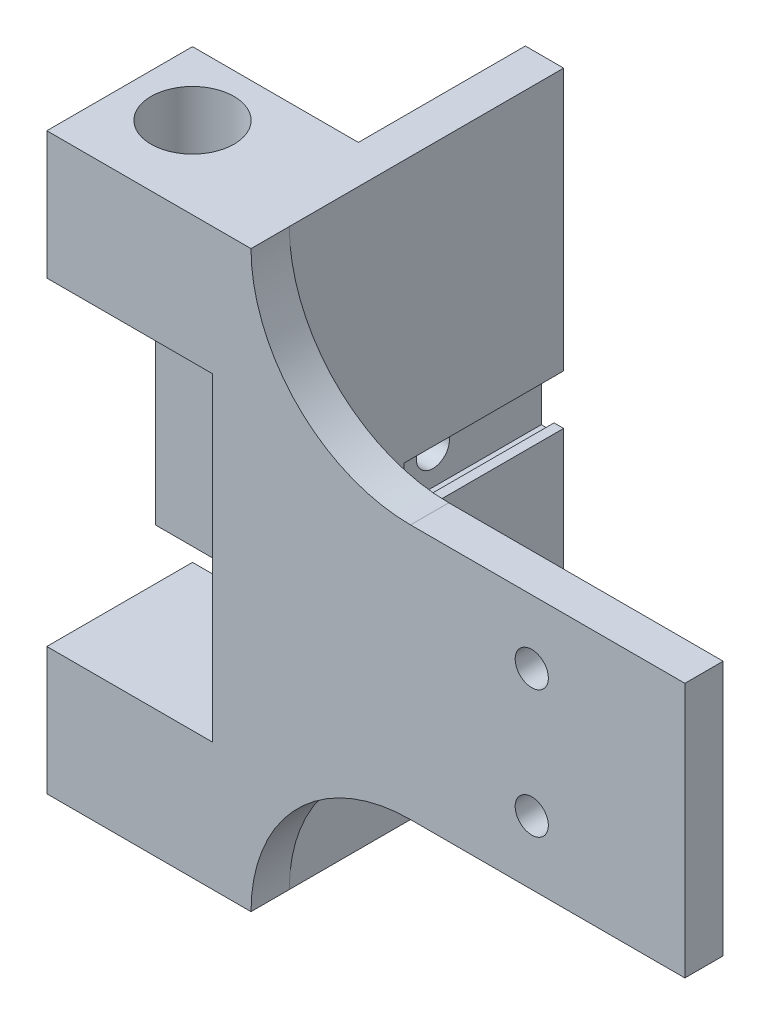
SolidWorks part; units mm, degrees
ref_plane "Front Plane" through (0, 0, 0) normal (0, 0, 1) x (1, 0, 0)
ref_plane "Top Plane" through (0, 0, 0) normal (0, 1, 0) x (1, 0, 0)
ref_plane "Right Plane" through (0, 0, 0) normal (1, 0, 0) x (0, 0, -1)
sketch "Sketch1" plane through (0, 0, 0) normal (0, 0, 1) x (1, 0, 0)
  line L1 (0, 0) -> (74, 0)
  line L2 (0, 0) -> (0, 90)
  line L3 (0, 90) -> (74, 90)
  line L4 (74, 0) -> (74, 90)
  circle A0 centre (50, 55) radius 2.6
  circle A1 centre (50, 35) radius 2.6
  point P9 (0, 0)
  point P10 (0, 0)
  dimension "D3" = 5.2
  dimension "D4" = 5.2
  dimension "D1" = 90
  dimension "D2" = 74
  dimension "D5" = 50
  dimension "D6" = 50
  dimension "D7" = 20
  dimension "D8" = 35
extrude "Boss-Extrude1" add sketch "Sketch1" along normal blind 6
sketch "Sketch2" plane through (0, 0, 0) normal (0, 0, -1) x (-1, 0, 0)
  line L0 (0, 0) -> (-74, 0) construction
  line L1 (0, 90) -> (-6, 90)
  line L2 (0, 90) -> (0, 0)
  line L3 (0, 0) -> (-6, 0)
  line L4 (-6, 90) -> (-6, 0)
  dimension "D1" = 6
extrude "Boss-Extrude2" add sketch "Sketch2" along normal blind 43
sketch "Sketch4" plane through (0, 0, 0) normal (0, 0, -1) x (-1, 0, 0)
  line L0 (-6, 90) -> (-6, 0) construction
  line L1 (-74, 90) -> (-6, 90)
  line L2 (-74, 90) -> (-74, 65)
  line L3 (-74, 65) -> (-6, 65)
  line L4 (-6, 90) -> (-6, 65)
  line L5 (-6, 90) -> (-6, 0) construction
  line L6 (-74, 0) -> (-6, 0)
  line L7 (-74, 0) -> (-74, 25)
  line L8 (-74, 25) -> (-6, 25)
  line L9 (-6, 0) -> (-6, 25)
  dimension "D1" = 25
  dimension "D2" = 25
extrude "Cut-Extrude3" cut sketch "Sketch4" against normal blind 6
fillet "Fillet2" radius 25 2 edges at (6, 65, 3) (6, 25, 3)
sketch "Sketch5" plane through (0, 0, 0) normal (-1, 0, 0) x (0, 0, 1)
  line L0 (-43, 0) -> (-43, 90) construction
  line L1 (-43, 60) -> (-9, 60)
  line L2 (-43, 60) -> (-43, 30)
  line L3 (-43, 30) -> (-9, 30)
  line L4 (-9, 60) -> (-9, 30)
  line L5 (6, 0) -> (-43, 0) construction
  line L6 (6, 90) -> (6, 0) construction
  dimension "D1" = 30
  dimension "D2" = 30
  dimension "D3" = 15
extrude "Boss-Extrude3" add sketch "Sketch5" along normal blind 24
sketch "Sketch3" plane through (0, 0, 0) normal (-1, 0, 0) x (0, 0, 1)
  line L0 (6, 90) -> (6, 0) construction
  line L1 (6, 0) -> (-43, 0) construction
  circle A0 centre (-26, 45) radius 2.6
  dimension "D2" = 5.2
  dimension "D1" = 32
  dimension "D3" = 45
extrude "Cut-Extrude1" cut sketch "Sketch3" against normal through all both and the other way through all
sketch "Sketch6" plane through (0, 60, 0) normal (0, 1, 0) x (1, 0, 0)
  line L0 (-24, 9) -> (-24, 43) construction
  line L1 (-3.75, 40) -> (-21, 40)
  line L2 (-3.75, 40) -> (-3.75, 12)
  line L3 (-3.75, 12) -> (-21, 12)
  line L4 (-21, 40) -> (-21, 12)
  line L5 (-24, 9) -> (0, 9) construction
  line L7 (-24, 43) -> (0, 43) construction
  line L8 (0, 9) -> (0, 43) construction
  dimension "D1" = 3
  dimension "D2" = 3
  dimension "D3" = 3
  dimension "D4" = 3.75
extrude "Cut-Extrude4" cut sketch "Sketch6" against normal through all
sketch "Sketch7" plane through (0, 0, -43) normal (0, 0, -1) x (-1, 0, 0)
  line L1 (-2.5, 50.15) -> (-4.5, 50.15)
  line L2 (-2.5, 50.15) -> (-2.5, 39.85)
  line L3 (-2.5, 39.85) -> (-4.5, 39.85)
  line L4 (-4.5, 50.15) -> (-4.5, 48.9)
  line L5 (24, 60) -> (0, 60) construction
  line L6 (-6, 90) -> (-6, 0) construction
  line L7 (-4.5, 41.1) -> (-4.5, 39.85)
  line L8 (-4.5, 48.9) -> (-7.5, 48.9)
  line L10 (-4.5, 41.1) -> (-7.5, 41.1)
  line L11 (-7.5, 48.9) -> (-7.5, 41.1)
  dimension "D1" = 10.3
  dimension "D2" = 2
  dimension "D3" = 9.85
  dimension "D4" = 1.5
  dimension "D6" = 1.25
  dimension "D5" = 1.25
extrude "Cut-Extrude5" cut sketch "Sketch7" against normal blind 25
sketch "Sketch8" plane through (0, 0, 0) normal (-1, 0, 0) x (0, 0, 1)
  line L0 (6, 90) -> (6, 0) construction
  line L1 (6, 0) -> (-16.83, 0)
  line L2 (6, 0) -> (6, 20)
  line L3 (6, 20) -> (-16.83, 20)
  line L4 (-16.83, 0) -> (-16.83, 20)
  line L5 (6, 90) -> (-43, 90) construction
  line L6 (-16.83, 70) -> (6, 70)
  line L7 (-16.83, 70) -> (-16.83, 90)
  line L8 (-16.83, 90) -> (6, 90)
  line L9 (6, 70) -> (6, 90)
  dimension "D1" = 20
  dimension "D2" = 0
  dimension "D3" = 22.83
  dimension "D4" = 0
  dimension "D5" = 0
  dimension "D6" = 20
  dimension "D7" = 22.83
extrude "Boss-Extrude4" add sketch "Sketch8" along normal blind 26
sketch "Sketch9" plane through (0, 0, 0) normal (0, -1, 0) x (1, 0, 0)
  line L0 (-26, -16.83) -> (0, -16.83) construction
  line L1 (-26, -16.83) -> (-26, 6) construction
  circle A0 centre (-16, -6.83) radius 6.5
  dimension "D1" = 13
  dimension "D2" = 10
  dimension "D3" = 10
extrude "Cut-Extrude6" cut sketch "Sketch9" against normal blind 10
sketch "Sketch10" plane through (0, 90, 0) normal (0, 1, 0) x (1, 0, 0)
  line L0 (-26, -6) -> (-26, 16.83) construction
  line L1 (-26, 16.83) -> (0, 16.83) construction
  circle A0 centre (-16, 6.83) radius 6.5
  dimension "D1" = 13
  dimension "D2" = 10
  dimension "D3" = 10
extrude "Cut-Extrude7" cut sketch "Sketch10" against normal blind 10
equation "\"D6@Sketch1\"=\"D5@Sketch1\""
equation "\"D8@Sketch1\"=(\"D1@Sketch1\"-\"D7@Sketch1\")/2"
equation "\"D3@Sketch7\"=(30-\"D1@Sketch7\")/2"
